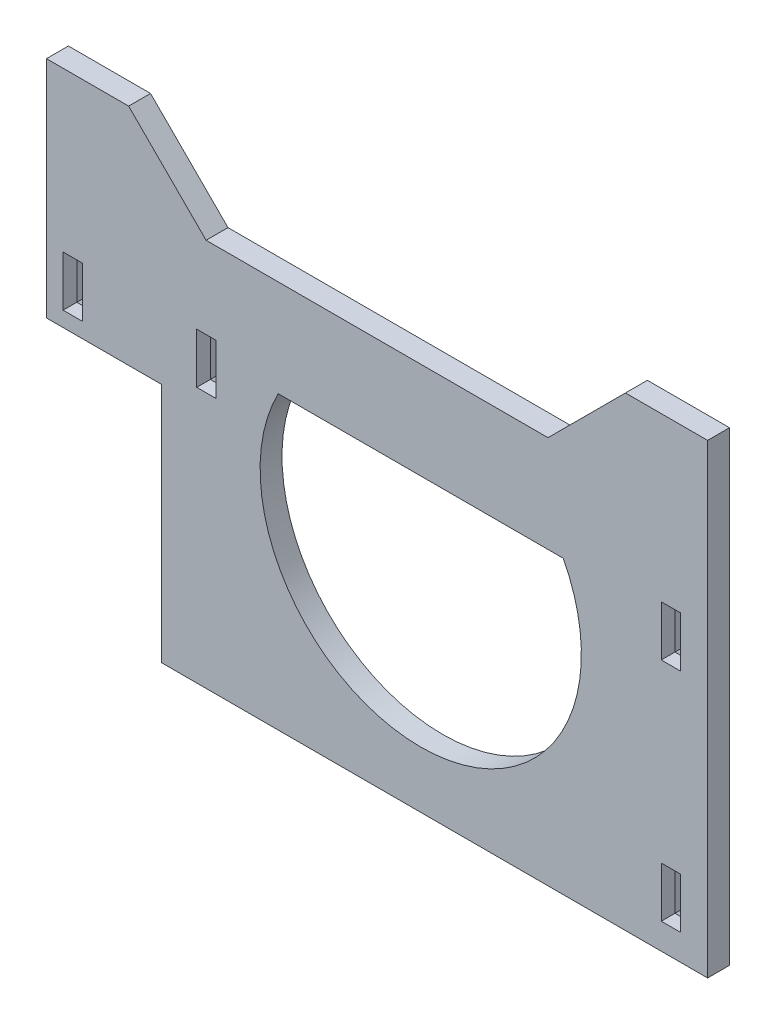
SolidWorks part; units mm, degrees
ref_plane "Front Plane" through (0, 0, 0) normal (0, 0, 1) x (1, 0, 0)
ref_plane "Top Plane" through (0, 0, 0) normal (0, 1, 0) x (1, 0, 0)
ref_plane "Right Plane" through (0, 0, 0) normal (1, 0, 0) x (0, 0, -1)
sketch "Sketch1" plane through (0, 0, 0) normal (0, 0, 1) x (1, 0, 0)
  line L0 (-25.9, 23.1791) -> (26.1356, 23.1791)
  line L6 (-40.7725, 25.95) -> (-37.2425, 25.95)
  line L9 (-40.7725, 25.95) -> (-40.7725, 16.75)
  line L12 (-40.7725, 16.75) -> (-37.2425, 16.75)
  line L15 (-37.2425, 25.95) -> (-37.2425, 16.75)
  line L51 (52.4925, 30) -> (52.4925, -30)
  line L54 (44.0275, 25.25) -> (47.5575, 25.25)
  line L55 (44.0275, 25.25) -> (44.0275, 16.05)
  line L56 (44.0275, 16.05) -> (47.5575, 16.05)
  line L57 (47.5575, 25.25) -> (47.5575, 16.05)
  line L58 (47.565, -16.05) -> (44.035, -16.05)
  line L59 (47.565, -16.05) -> (47.565, -25.25)
  line L60 (47.565, -25.25) -> (44.035, -25.25)
  line L61 (44.035, -16.05) -> (44.035, -25.25)
  line L65 (-65.1725, 25.95) -> (-61.6425, 25.95)
  line L66 (-65.1725, 25.95) -> (-65.1725, 16.75)
  line L67 (-65.1725, 16.75) -> (-61.6425, 16.75)
  line L68 (-61.6425, 25.95) -> (-61.6425, 16.75)
  line L76 (52.4925, 30) -> (-68.2075, 30)
  line L81 (-39.0075, 25.95) -> (-39.0075, 16.75) construction
  line L82 (-37.2425, 21.35) -> (-40.7725, 21.35) construction
  line L83 (-63.4075, 25.95) -> (-63.4075, 16.75) construction
  line L84 (-61.6425, 21.35) -> (-65.1725, 21.35) construction
  line L85 (47.5575, 20.65) -> (44.0275, 20.65) construction
  line L86 (45.7925, 25.25) -> (45.7925, 16.05) construction
  line L87 (45.8, -16.05) -> (45.8, -25.25) construction
  line L88 (47.565, -20.65) -> (44.035, -20.65) construction
  line L89 (-47.2075, -30) -> (-47.2075, 14)
  line L90 (-47.2075, 14) -> (-68.2075, 14)
  line L91 (-68.2075, 14) -> (-68.2075, 30)
  line L92 (-47.2075, -30) -> (52.4925, -30)
  arc A12 (-25.9, 23.1791) -> (26.1356, 23.1791) centre (0.1178, 9.6488) ccw
  point P0 (-0.0075, 0)
  point P14 (52.4925, 0)
  point P25 (-7.8575, 30)
  dimension "D3" = 3.53
  dimension "D4" = 9.2
  dimension "D6" = 60
  dimension "D5" = 24.4
  dimension "D7" = 53.65
  dimension "D2" = 31.15
  dimension "D10" = 20.65
  dimension "D11" = 20.65
  dimension "D8" = 120.7
  dimension "D9" = 21
  dimension "D12" = 44
extrude "Boss-Extrude1" add sketch "Sketch1" along normal blind 4
sketch "Sketch2" plane through (0, 0, 0) normal (0, 0, 1) x (1, 0, 0)
  line L0 (-68.2075, 30) -> (52.4925, 30)
  line L4 (23.3504, 40.8579) -> (-39.0654, 40.8579)
  line L5 (-39.0654, 40.8579) -> (-53.2075, 55)
  line L6 (-53.2075, 55) -> (-68.2075, 55)
  line L7 (-68.2075, 55) -> (-68.2075, 30)
  line L8 (23.3504, 40.8579) -> (37.4925, 55)
  line L9 (37.4925, 55) -> (52.4925, 55)
  line L10 (52.4925, 55) -> (52.4925, 30)
  line L12 (-68.2075, 30) -> (-68.2075, 14) construction
  dimension "D1" = 25
  dimension "D2" = 20
  dimension "D3" = 15
  dimension "D4" = 135
extrude "Boss-Extrude2" add sketch "Sketch2" along normal blind 4
sketch "Sketch3" plane through (0, 0, 0) normal (0, 0, -1) x (-1, 0, 0)
  line L0 (-45.7925, 25.25) -> (-45.7925, 16.05) construction
  line L1 (-47.5575, 25.25) -> (-44.0275, 25.25) construction
  line L2 (-44.0275, 16.05) -> (-47.5575, 16.05) construction
  line L3 (-47.5575, 20.65) -> (-44.0275, 20.65) construction
  line L4 (-47.5575, 16.05) -> (-47.5575, 25.25) construction
  line L5 (-44.0275, 25.25) -> (-44.0275, 16.05) construction
  line L6 (-45.8, -16.05) -> (-45.8, -25.25) construction
  line L7 (-47.565, -16.05) -> (-44.035, -16.05) construction
  line L8 (-44.035, -25.25) -> (-47.565, -25.25) construction
  line L9 (-47.565, -20.65) -> (-44.035, -20.65) construction
  line L10 (-47.565, -25.25) -> (-47.565, -16.05) construction
  line L11 (-44.035, -16.05) -> (-44.035, -25.25) construction
  line L12 (39.0075, 25.95) -> (39.0075, 16.75) construction
  line L13 (37.2425, 25.95) -> (40.7725, 25.95) construction
  line L14 (40.7725, 16.75) -> (37.2425, 16.75) construction
  line L15 (37.2425, 21.35) -> (40.7725, 21.35) construction
  line L16 (37.2425, 16.75) -> (37.2425, 25.95) construction
  line L17 (40.7725, 25.95) -> (40.7725, 16.75) construction
  line L18 (63.4075, 25.95) -> (63.4075, 16.75) construction
  line L19 (61.6425, 25.95) -> (65.1725, 25.95) construction
  line L20 (65.1725, 16.75) -> (61.6425, 16.75) construction
  line L21 (61.6425, 21.35) -> (65.1725, 21.35) construction
  line L22 (61.6425, 16.75) -> (61.6425, 25.95) construction
  line L23 (65.1725, 25.95) -> (65.1725, 16.75) construction
chamfer "Chamfer1" distance 1.5 distance2 0.5 16 edges at (45.8, -25.25, 0) (44.035, -20.65, 0) (45.8, -16.05, 0) (47.565, -20.65, 0) (-63.4075, 25.95, 0) (-61.6425, 21.35, 0) (-63.4075, 16.75, 0) (-65.1725, 21.35, 0) (-39.0075, 25.95, 0) (-37.2425, 21.35, 0) (-39.0075, 16.75, 0) (-40.7725, 21.35, 0) (45.7925, 25.25, 0) (47.5575, 20.65, 0) (45.7925, 16.05, 0) (44.0275, 20.65, 0) first distance on face at (45.8, -25.25, 2) first distance on face at (44.035, -20.65, 2) first distance on face at (45.8, -16.05, 2) first distance on face at (47.565, -20.65, 2) first distance on face at (-63.4075, 25.95, 2) first distance on face at (-61.6425, 21.35, 2) first distance on face at (-63.4075, 16.75, 2) first distance on face at (-65.1725, 21.35, 2) first distance on face at (-39.0075, 25.95, 2) first distance on face at (-37.2425, 21.35, 2) first distance on face at (-39.0075, 16.75, 2) first distance on face at (-40.7725, 21.35, 2) first distance on face at (45.7925, 25.25, 2) first distance on face at (47.5575, 20.65, 2) first distance on face at (45.7925, 16.05, 2) first distance on face at (44.0275, 20.65, 2)
equation "\"pin_hole_width\"=3.53"
equation "\"D3@Sketch1\"=\"pin_hole_width\""
equation "\"pin_hole_height\"=9.2"
equation "\"D4@Sketch1\"=\"pin_hole_height\""
equation "\"distancer\"=24.4"
equation "\"D5@Sketch1\"=\"distancer\""
